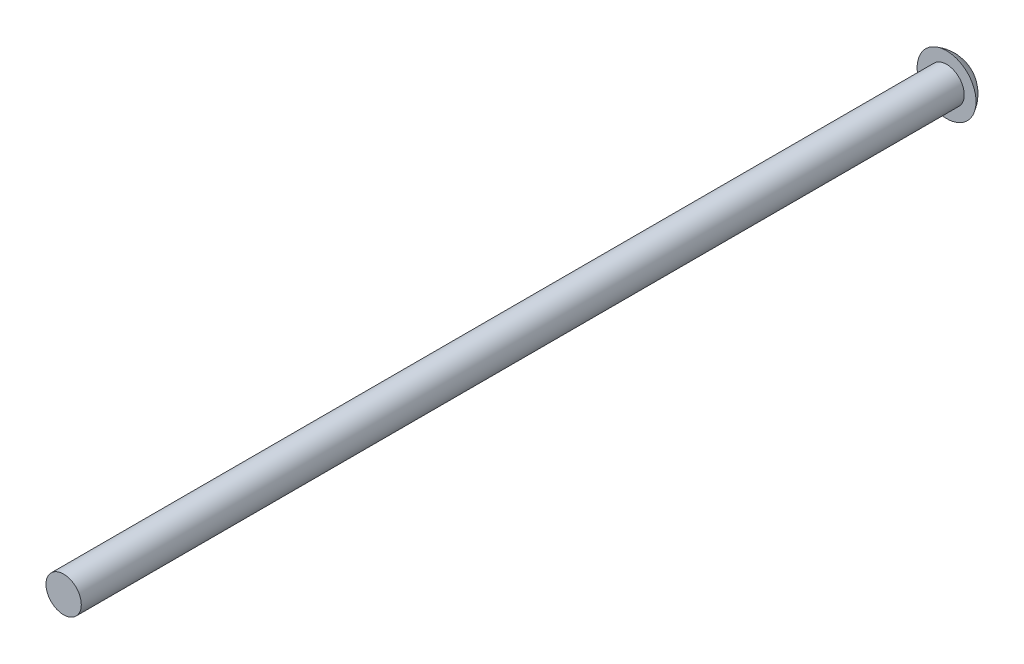
SolidWorks part; units mm, degrees
material "镀铬不锈钢"
ref_plane "前视基准面" through (0, 0, 0) normal (0, 0, 1) x (1, 0, 0)
ref_plane "上视基准面" through (0, 0, 0) normal (0, 1, 0) x (1, 0, 0)
ref_plane "右视基准面" through (0, 0, 0) normal (1, 0, 0) x (0, 0, -1)
sketch "草图1" plane through (0, 0, 0) normal (0, 0, 1) x (1, 0, 0)
  circle A0 centre (0, 0) radius 3
  dimension "D1" = 6
extrude "凸台-拉伸1" add sketch "草图1" along normal blind 150
sketch "草图2" plane through (0, 0, 0) normal (0, 1, 0) x (1, 0, 0)
  line L0 (0, 0) -> (5, 0)
  line L1 (0, 0) -> (0, 3)
  arc A0 (0, 3) -> (5, 0) centre (0, -2.6667) cw
  dimension "D1" = 5
  dimension "D2" = 3
revolve "旋转1" add sketch "草图2" angle 360 about L1
